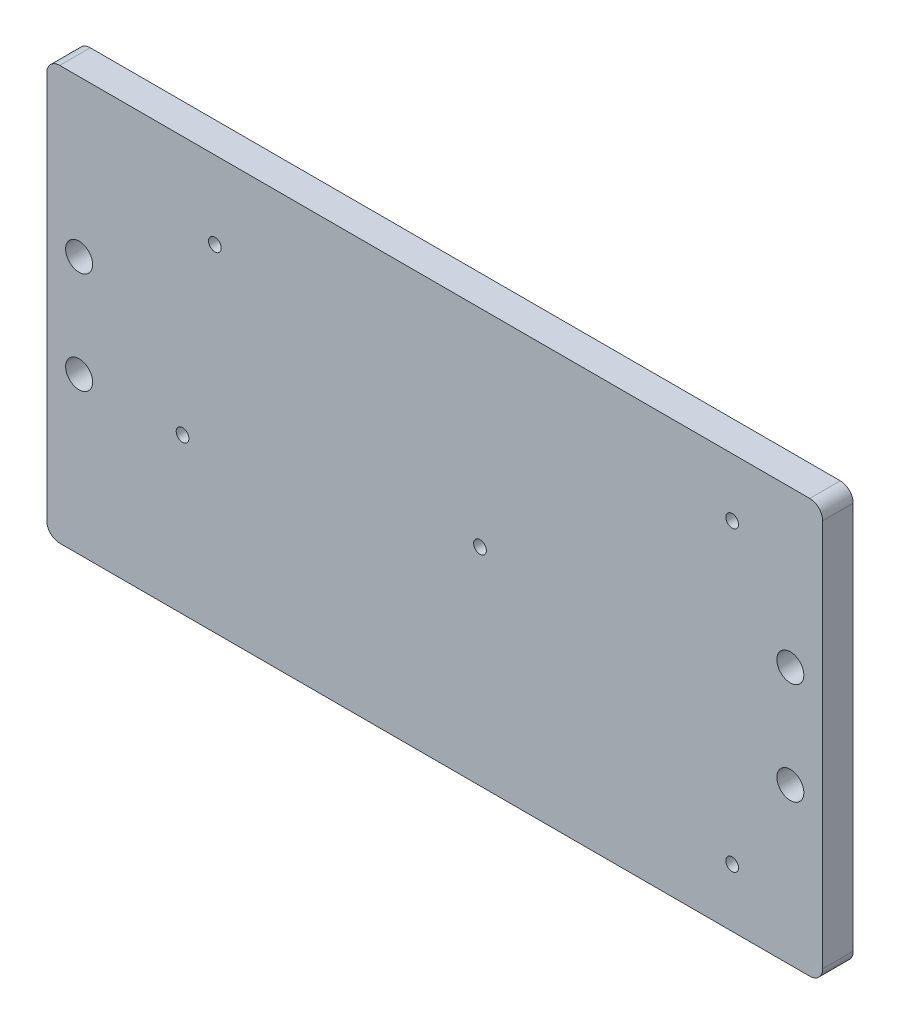
SolidWorks part; units mm, degrees
material "Perspex (TM) GS Acrylic Cast Sheet"
ref_plane "Front Plane" through (0, 0, 0) normal (0, 0, 1) x (1, 0, 0)
ref_plane "Top Plane" through (0, 0, 0) normal (0, 1, 0) x (1, 0, 0)
ref_plane "Right Plane" through (0, 0, 0) normal (1, 0, 0) x (0, 0, -1)
other "Configuration Table"
ref_plane "Plane1" through (0, 0, -12) normal (0, 0, -1) x (-1, 0, 0)
sketch "Sketch1" plane through (0, 0, -12) normal (0, 0, -1) x (-1, 0, 0)
  line L0 (-527.9771, 394.1064) -> (-375.5771, 394.1064) construction
  line L1 (-525.4371, 434.7464) -> (-378.1171, 434.7464)
  line L2 (-527.9771, 432.2064) -> (-527.9771, 356.0064)
  line L3 (-525.4371, 353.4664) -> (-378.1171, 353.4664)
  line L4 (-399.7071, 428.3964) -> (-512.7371, 428.3964)
  line L5 (-515.2771, 425.8564) -> (-515.2771, 362.3564)
  line L6 (-512.7371, 359.8164) -> (-399.7071, 359.8164)
  line L7 (-397.1671, 362.3564) -> (-397.1671, 425.8564)
  line L16 (-399.7071, 428.3964) -> (-512.7371, 428.3964) construction
  line L17 (-515.2771, 425.8564) -> (-515.2771, 362.3564) construction
  line L18 (-512.7371, 359.8164) -> (-399.7071, 359.8164) construction
  line L19 (-397.1671, 362.3564) -> (-397.1671, 425.8564) construction
  line L20 (-375.5771, 432.2064) -> (-375.5771, 356.0064)
  line L21 (-527.9771, 404.1064) -> (-375.5771, 404.1064) construction
  line L22 (-375.5771, 384.1064) -> (-527.9771, 384.1064) construction
  line L23 (-451.7771, 404.1064) -> (-451.7771, 394.1064) construction
  line L24 (-451.7771, 394.1064) -> (-451.7771, 384.1064) construction
  line L25 (-527.9771, 404.1064) -> (-521.6271, 404.1064) construction
  line L26 (-521.6271, 404.1064) -> (-515.2771, 404.1064) construction
  circle A0 centre (-510.1971, 364.8964) radius 1.575 construction
  circle A1 centre (-402.2471, 383.9464) radius 1.575 construction
  circle A2 centre (-408.5971, 419.5064) radius 1.575 construction
  circle A3 centre (-460.6671, 394.1064) radius 1.575 construction
  arc A4 (-397.1671, 425.8564) -> (-399.7071, 428.3964) centre (-399.7071, 425.8564) ccw
  arc A5 (-512.7371, 428.3964) -> (-515.2771, 425.8564) centre (-512.7371, 425.8564) ccw
  arc A6 (-515.2771, 362.3564) -> (-512.7371, 359.8164) centre (-512.7371, 362.3564) ccw
  arc A7 (-399.7071, 359.8164) -> (-397.1671, 362.3564) centre (-399.7071, 362.3564) ccw
  arc A16 (-397.1671, 425.8564) -> (-399.7071, 428.3964) centre (-399.7071, 425.8564) ccw construction
  arc A17 (-512.7371, 428.3964) -> (-515.2771, 425.8564) centre (-512.7371, 425.8564) ccw construction
  arc A18 (-515.2771, 362.3564) -> (-512.7371, 359.8164) centre (-512.7371, 362.3564) ccw construction
  arc A19 (-399.7071, 359.8164) -> (-397.1671, 362.3564) centre (-399.7071, 362.3564) ccw construction
  circle A20 centre (-510.1971, 423.3164) radius 1.575 construction
  circle A21 centre (-510.1971, 364.8964) radius 1.575 construction
  circle A22 centre (-402.2471, 383.9464) radius 1.575 construction
  circle A23 centre (-408.5971, 419.5064) radius 1.575 construction
  circle A24 centre (-460.6671, 394.1064) radius 1.575 construction
  circle A25 centre (-510.1971, 423.3164) radius 1.575 construction
  circle A26 centre (-521.6271, 404.1064) radius 6 construction
  circle A27 centre (-521.6271, 384.1064) radius 6 construction
  circle A28 centre (-381.9271, 384.1064) radius 6 construction
  circle A29 centre (-381.9271, 404.1064) radius 6 construction
  arc A30 (-378.1171, 434.7464) -> (-375.5771, 432.2064) centre (-378.1171, 432.2064) cw
  arc A31 (-378.1171, 353.4664) -> (-375.5771, 356.0064) centre (-378.1171, 356.0064) ccw
  arc A32 (-527.9771, 356.0064) -> (-525.4371, 353.4664) centre (-525.4371, 356.0064) ccw
  arc A33 (-525.4371, 434.7464) -> (-527.9771, 432.2064) centre (-525.4371, 432.2064) ccw
  point P33 (-515.2771, 394.1064)
  dimension "D3" = 12
  dimension "D4" = 69.85
  dimension "D8" = 2.54
  dimension "D2" = 20
  dimension "D5" = 69.85
  dimension "D6" = 12.7
  dimension "D7" = 6.35
  dimension "D1" = 0
extrude "Boss-Extrude1" add sketch "Sketch1" along normal blind 6
hole_wizard "M5 Clearance Hole1" positions "Sketch3" profile "Sketch4" hole size "M5" standard "ANSI Metric" end condition through all
sketch "Sketch3" plane through (0, 0, -18) normal (0, 0, -1) x (-1, 0, 0)
  point P0 (-521.6271, 404.1064)
  point P3 (-521.6271, 384.1064)
  point P6 (-381.9271, 384.1064)
  point P9 (-381.9271, 404.1064)
sketch "Sketch4" plane through (521.6271, 404.1064, -18) normal (1, 0, 0) x (0, 1, 0)
  line L0 (0, 0) -> (0, 6)
  line L1 (0, 6) -> (2.65, 6)
  line L2 (2.65, 6) -> (2.65, 0)
  line L5 (2.65, 0) -> (0, 0)
  line L11 (0, -6.35) -> (0, 107.95) construction
  dimension "Thru Hole Dia." = 5.3
  dimension "Thru Hole Depth" = 6
hole_wizard "M3x0.5 Tapped Hole1" positions "Sketch5" profile "Sketch6" tap size "M3x0.5" standard "ANSI Metric" end condition through all
sketch "Sketch5" plane through (0, 0, -18) normal (0, 0, -1) x (-1, 0, 0)
  point P0 (-510.1971, 423.3164)
  point P3 (-408.5971, 419.5064)
  point P6 (-460.6671, 394.1064)
  point P9 (-402.2471, 383.9464)
  point P12 (-510.1971, 364.8964)
sketch "Sketch6" plane through (510.1971, 423.3164, -18) normal (1, 0, 0) x (0, 1, 0)
  line L0 (0, 0) -> (0, 6)
  line L1 (0, 6) -> (1.25, 6)
  line L2 (1.25, 6) -> (1.25, 0)
  line L5 (1.25, 0) -> (0, 0)
  line L11 (0, -6.35) -> (0, 107.95) construction
  dimension "Thru Tap Drill Dia." = 2.5
  dimension "Thru Tap Drill Depth" = 6
cosmetic thread "Hole Thread1" parameters "D2"=3
cosmetic thread "Hole Thread2" parameters "D2"=3
cosmetic thread "Hole Thread3" parameters "D2"=3
cosmetic thread "Hole Thread4" parameters "D2"=3
cosmetic thread "Hole Thread5" parameters "D2"=3
